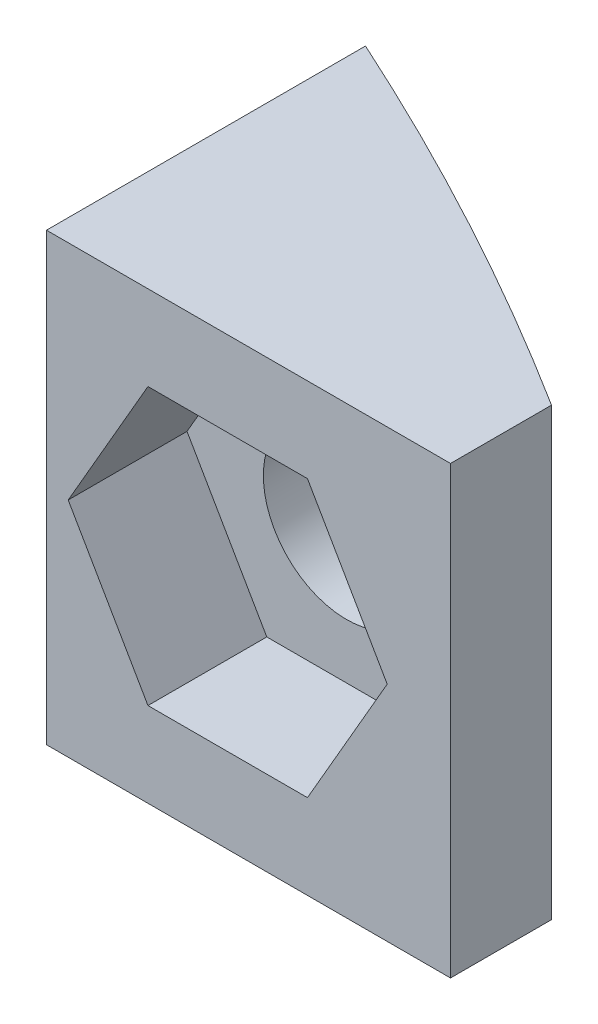
SolidWorks part; units mm, degrees
ref_plane "Front Plane" through (0, 0, 0) normal (0, 0, 1) x (1, 0, 0)
ref_plane "Top Plane" through (0, 0, 0) normal (0, 1, 0) x (1, 0, 0)
ref_plane "Right Plane" through (0, 0, 0) normal (1, 0, 0) x (0, 0, -1)
sketch "Sketch1" plane through (0, 0, 0) normal (0, 1, 0) x (1, 0, 0)
  line L0 (-58.42, 133.0252) -> (58.42, 133.0252)
  line L1 (60.198, 118.5925) -> (60.198, 132.2301)
  line L2 (60.198, 118.5925) -> (77.47, 118.5925)
  line L3 (77.47, 118.5925) -> (77.47, 122.9105)
  circle A0 centre (0, 0) radius 145.288
  dimension "D1" = 290.576
  dimension "D2" = 116.84
  dimension "D3" = 4.318
  dimension "D4" = 17.272
  dimension "D5" = 1.778
extrude "Boss-Extrude1" add sketch "Sketch1" along normal blind 19.05 contours L3 A0 L2 region at (67.3823, 0, -123.599)
sketch "Sketch2" plane through (0, 0, -118.5925) normal (0, 0, 1) x (1, 0, 0)
  line L0 (67.945, 19.05) -> (67.945, 0) construction
  line L1 (74.7641, 9.525) -> (71.3545, 15.4305)
  line L2 (71.3545, 15.4305) -> (64.5355, 15.4305)
  line L3 (64.5355, 15.4305) -> (61.1259, 9.525)
  line L4 (61.1259, 9.525) -> (64.5355, 3.6195)
  line L5 (64.5355, 3.6195) -> (71.3545, 3.6195)
  line L6 (71.3545, 3.6195) -> (74.7641, 9.525)
  line L7 (60.198, 19.05) -> (77.47, 19.05) construction
  line L9 (60.198, 0) -> (77.47, 0) construction
  line L10 (60.198, 9.525) -> (77.47, 9.525) construction
  line L11 (77.47, 19.05) -> (77.47, 0) construction
  line L12 (60.198, 19.05) -> (60.198, 0) construction
  circle A0 centre (67.945, 9.525) radius 5.9055 construction
  circle A1 centre (67.945, 9.525) radius 3.556
  dimension "D1" = 11.811
  dimension "D3" = 7.112
  dimension "D2" = 9.525
extrude "Cut-Extrude1" cut sketch "Sketch2" against normal blind 5.08 contours A1 | L5 L6 L1 L2 L3 L4 A1 region at (72.9031, 6.6625, -118.5925) region at (67.945, 9.525, -118.5925)
extrude "Cut-Extrude2" cut sketch "Sketch2<3>" against normal up to surface (7.8836 mm away) contours A1 region at (67.945, 9.525, -118.5925) up to face at (68.9128, 9.525, -127.7163)
sketch "Sketch2<3>" plane through (0, 0, -118.5925) normal (0, 0, 1) x (1, 0, 0) same geometry as "Sketch2"
